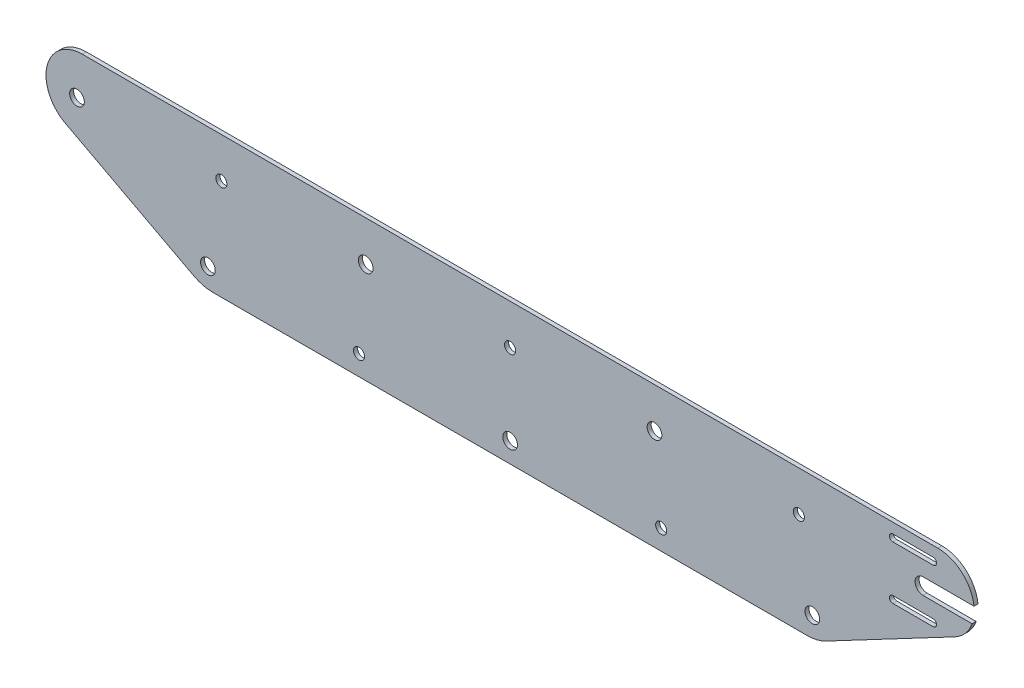
SolidWorks part; units mm, degrees
ref_plane "Plan de face" through (0, 0, 0) normal (0, 0, 1) x (1, 0, 0)
ref_plane "Plan de dessus" through (0, 0, 0) normal (0, 1, 0) x (1, 0, 0)
ref_plane "Plan de droite" through (0, 0, 0) normal (1, 0, 0) x (0, 0, -1)
sketch "Esquisse1" plane through (0, 0, 0) normal (0, 0, 1) x (1, 0, 0)
  line L0 (0, 0) -> (0, 122.747) construction
  line L1 (-215, -20) -> (215, -20) construction
  line L2 (-215, -20) -> (-215, 20) construction
  line L3 (-215, 20) -> (215, 20) construction
  line L4 (215, -20) -> (215, 20) construction
  line L5 (-215, -20) -> (215, 20) construction
  line L6 (-215, 20) -> (215, -20) construction
  line L7 (-1220, 0) -> (-150, 0) construction
  line L8 (-284.959, 40) -> (-150, 40)
  line L9 (150, 40) -> (284.959, 40)
  line L10 (150, 0) -> (150, -20) construction
  line L11 (150, -20) -> (-150, -20) construction
  line L12 (-150, 0) -> (-150, -20) construction
  line L13 (150, 0) -> (-150, -20) construction
  line L14 (150, -20) -> (-150, 0) construction
  line L15 (-284.959, 40) -> (-152.4795, -30)
  line L16 (-152.4795, -30) -> (152.4795, -30)
  line L17 (284.959, 40) -> (152.4795, -30)
  line L18 (-215, 20) -> (-71.6667, 20) construction
  line L19 (-71.6667, 20) -> (71.6667, 20) construction
  line L20 (71.6667, 20) -> (215, 20) construction
  line L21 (150, 0) -> (193.5165, 0) construction
  line L22 (150, 95) -> (-150, 95) construction
  line L23 (150, 95) -> (150, 40) construction
  line L24 (-150, 40) -> (150, 40)
  line L25 (-150, 95) -> (-150, 40) construction
  line L26 (150, 95) -> (-150, 0) construction
  line L27 (150, 0) -> (-150, 95) construction
  circle A0 centre (-215, 20) radius 3.65
  circle A1 centre (-150, -20) radius 3.65
  circle A2 centre (150, -20) radius 3.65
  circle A3 centre (215, 20) radius 3.65
  circle A4 centre (0, -20) radius 3.65
  circle A5 centre (-71.6667, 20) radius 3.65
  circle A6 centre (71.6667, 20) radius 3.65
  circle A7 centre (0, 78.03) radius 3.65 construction
  point P0 (0, 0)
  point P8 (0, -10)
  point P20 (0, 47.5)
  point P21 (0, -30)
  point P31 (0, 47.5)
  dimension "D8" = 7.3
  dimension "D10" = 58.03
  dimension "D1" = 430
  dimension "D2" = 40
  dimension "D3" = 300
  dimension "D4" = 20
  dimension "D5" = 15
  dimension "D6" = 10
  dimension "D7" = 10
  dimension "D9" = 55
extrude "Boss.-Extru.1" add sketch "Esquisse1" along normal blind 2
fillet "Congé1" radius 18 2 edges at (-284.959, 40, 1) (284.959, 40, 1)
fillet "Congé2" radius 20 2 edges at (-152.4795, -30, 1) (152.4795, -30, 1)
hole_wizard "Dégagement M31" positions "Esquisse3" profile "Esquisse2" hole size "M3" standard "Ansi Metric" end condition through all
sketch "Esquisse3" plane through (0, 0, 0) normal (0, 0, -1) x (-1, 0, 0)
  line L0 (-215, 12.5) -> (-215, 20)
  line L1 (-200, 6.7712) -> (-200, 33.2288)
  circle A0 centre (-215, 20) radius 7.5
  circle A1 centre (-215, 20) radius 20
  point P0 (-200, 33.2288)
  point P29 (-200, 6.7712)
  dimension "D2" = 15
  dimension "D3" = 40
  dimension "D1" = 15
sketch "Esquisse2" plane through (200, 33.2288, 0) normal (1, 0, 0) x (0, 1, 0)
  line L0 (0, 0) -> (0, 2)
  line L1 (0, 2) -> (1.7, 2)
  line L2 (1.7, 2) -> (1.7, 0)
  line L5 (1.7, 0) -> (0, 0)
  line L11 (0, -6.35) -> (0, 107.95) construction
  dimension "Diamètre du perçage jusqu'au prochain" = 3.4
  dimension "Profondeur du perçage jusqu'au prochain" = 2
sketch "Esquisse4" plane through (0, 0, 0) normal (0, 0, -1) x (-1, 0, 0)
  line L0 (-215, 24) -> (-230.2521, 24)
  line L1 (-215, 24) -> (-205, 24)
  line L2 (-215, 16) -> (-205, 16)
  line L3 (-215, 16) -> (-229.3341, 16)
  line L4 (-147.5205, -30) -> (147.5205, -30)
  line L5 (156.8641, -27.6833) -> (220.7728, 6.0851)
  line L6 (212.3636, 40) -> (-212.3636, 40)
  line L7 (-220.7728, 6.0851) -> (-156.8641, -27.6833)
  line L8 (-147.5205, -30) -> (147.5205, -30)
  line L9 (156.8641, -27.6833) -> (220.7728, 6.0851)
  line L10 (212.3636, 40) -> (-212.3636, 40)
  line L11 (-220.7728, 6.0851) -> (-156.8641, -27.6833)
  line L12 (-215, 16) -> (-215, 24)
  line L13 (-200, 34.9288) -> (-210, 34.9288)
  line L14 (-200, 34.9288) -> (-200, 31.5288)
  line L15 (-210, 31.5288) -> (-200, 31.5288)
  line L16 (-200, 31.5288) -> (-190, 31.5288)
  line L17 (-200, 8.4712) -> (-210, 8.4712)
  line L18 (-190, 34.9288) -> (-200, 34.9288)
  line L19 (-200, 8.4712) -> (-200, 5.0712)
  line L20 (-210, 5.0712) -> (-200, 5.0712)
  line L21 (-200, 5.0712) -> (-190, 5.0712)
  line L22 (-190, 8.4712) -> (-200, 8.4712)
  line L23 (-175, 14.2) -> (-185, 14.2)
  line L24 (-175, 14.2) -> (-175, 10.8)
  line L25 (-185, 10.8) -> (-175, 10.8)
  line L26 (-175, 10.8) -> (-165, 10.8)
  line L27 (-165, 14.2) -> (-175, 14.2)
  line L28 (-185, 14.2) -> (-228.5858, 14.2)
  line L29 (-185, 10.8) -> (-226.4547, 10.8)
  arc A2 (-205, 24) -> (-205, 16) centre (-205, 20) cw
  circle A3 centre (-215, 20) radius 3.65 construction
  arc A4 (147.5205, -30) -> (156.8641, -27.6833) centre (147.5205, -10) ccw
  arc A5 (220.7728, 6.0851) -> (212.3636, 40) centre (212.3636, 22) ccw
  arc A6 (-212.3636, 40) -> (-220.7728, 6.0851) centre (-212.3636, 22) ccw
  arc A7 (-156.8641, -27.6833) -> (-147.5205, -30) centre (-147.5205, -10) ccw
  arc A8 (147.5205, -30) -> (156.8641, -27.6833) centre (147.5205, -10) ccw
  arc A9 (220.7728, 6.0851) -> (212.3636, 40) centre (212.3636, 22) ccw
  arc A10 (-212.3636, 40) -> (-220.7728, 6.0851) centre (-212.3636, 22) ccw
  arc A11 (-156.8641, -27.6833) -> (-147.5205, -30) centre (-147.5205, -10) ccw
  circle A12 centre (-200, 33.2288) radius 1.7 construction
  circle A13 centre (-200, 33.2288) radius 1.7 construction
  arc A14 (-190, 34.9288) -> (-190, 31.5288) centre (-190, 33.2288) cw
  arc A15 (-210, 34.9288) -> (-210, 31.5288) centre (-210, 33.2288) ccw
  arc A16 (-190, 8.4712) -> (-190, 5.0712) centre (-190, 6.7712) cw
  arc A17 (-210, 8.4712) -> (-210, 5.0712) centre (-210, 6.7712) ccw
  arc A18 (-165, 14.2) -> (-165, 10.8) centre (-165, 12.5) cw
  circle A20 centre (-200, 6.7712) radius 1.7 construction
  point P17 (-215, 20)
  point P32 (-200, 33.2288)
  point P41 (-200, 6.7712)
  point P52 (-175, 12.5)
  dimension "D2" = 10
  dimension "D3" = 8
  dimension "D4" = 10
  dimension "D5" = 10
  dimension "D6" = 10
  dimension "D1" = 0
extrude "Enlèv. mat.-Extru.1" cut sketch "Esquisse4" against normal through all contours L3 A15 L0 A6 | A2 L1 A15 L2 | A14 L18 L2 L16 | L13 A15 L15 L2 | L17 A17 L20 L4 | A16 L22 L4 L21 region at (222.5529, 20.0401, 0) region at (208.3989, 20, 0) region at (205.6739, 33.2288, 0) region at (194.3261, 33.2288, 0) region at (205.6739, 6.7712, 0) region at (194.3261, 6.7712, 0)
hole_wizard "Dégagement M51" positions "Esquisse6" profile "Esquisse5" hole size "M5" standard "Ansi Metric" end condition through all
sketch "Esquisse6" plane through (0, 0, 0) normal (0, 0, -1) x (-1, 0, 0)
  line L0 (215, 20) -> (31.0935, 20) construction
  line L2 (215, 20) -> (143.3333, 20)
  line L4 (143.3333, 20) -> (71.6667, 20)
  line L5 (71.6667, 20) -> (0, 20)
  line L6 (0, 20) -> (-71.6667, 20)
  line L7 (-71.6667, 20) -> (-143.3333, 20)
  circle A2 centre (215, 20) radius 3.65
  circle A3 centre (215, 20) radius 3.65 construction
  circle A4 centre (-71.6667, 20) radius 3.65
  circle A5 centre (-71.6667, 20) radius 3.65 construction
  point P0 (143.3333, 20)
  point P2 (0, 20)
  point P37 (-143.3333, 20)
sketch "Esquisse5" plane through (-143.3333, 20, 0) normal (1, 0, 0) x (0, 1, 0)
  line L0 (0, 0) -> (0, 2)
  line L1 (0, 2) -> (2.75, 2)
  line L2 (2.75, 2) -> (2.75, 0)
  line L5 (2.75, 0) -> (0, 0)
  line L11 (0, -6.35) -> (0, 107.95) construction
  dimension "Diamètre du perçage jusqu'au prochain" = 5.5
  dimension "Profondeur du perçage jusqu'au prochain" = 2
hole_wizard "Dégagement M52" positions "Esquisse8" profile "Esquisse7" hole size "M5" standard "Ansi Metric" end condition through all
sketch "Esquisse8" plane through (0, 0, 2) normal (0, 0, 1) x (1, 0, 0)
  line L0 (-150, -20) -> (-75, -20)
  line L1 (-75, -20) -> (0, -20)
  line L2 (0, -20) -> (75, -20)
  line L3 (75, -20) -> (150, -20)
  point P0 (-75, -20)
  point P2 (75, -20)
sketch "Esquisse7" plane through (-75, -20, 2) normal (1, 0, 0) x (0, -1, 0)
  line L0 (0, 0) -> (0, 2)
  line L1 (0, 2) -> (2.75, 2)
  line L2 (2.75, 2) -> (2.75, 0)
  line L5 (2.75, 0) -> (0, 0)
  line L11 (0, -6.35) -> (0, 107.95) construction
  dimension "Diamètre du perçage jusqu'au prochain" = 5.5
  dimension "Profondeur du perçage jusqu'au prochain" = 2
